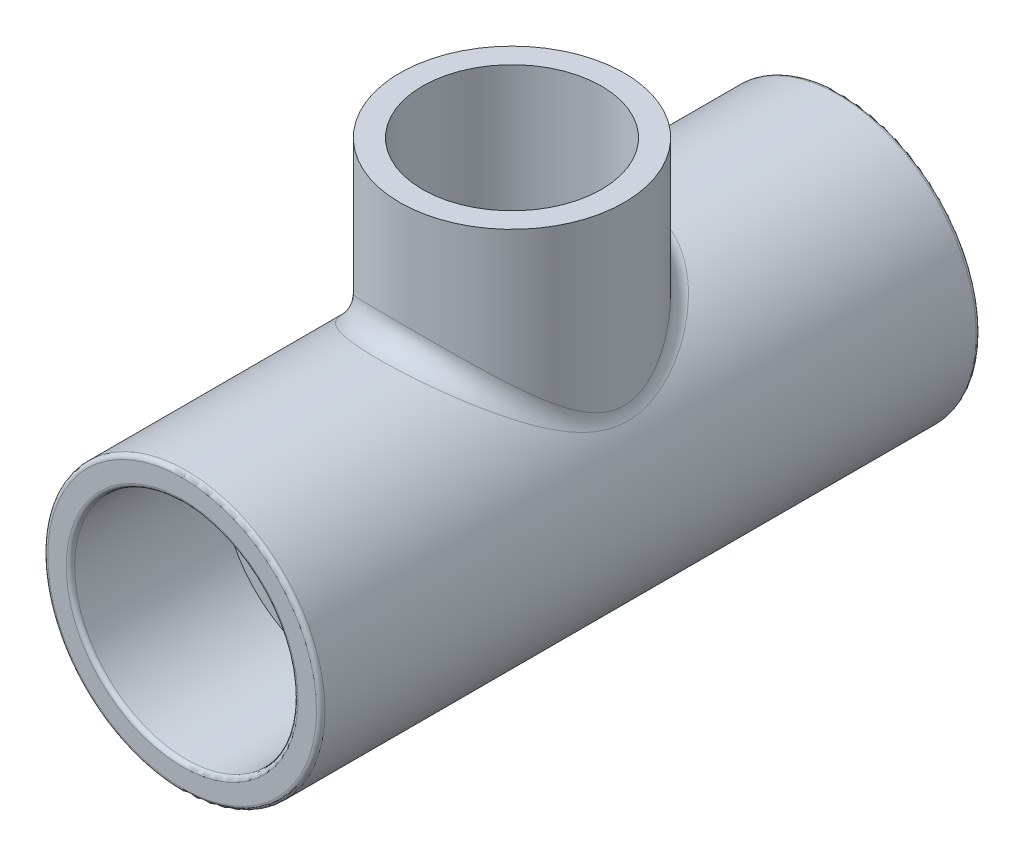
SolidWorks part; units mm, degrees
ref_plane "Front Plane" through (0, 0, 0) normal (0, 0, 1) x (1, 0, 0)
ref_plane "Top Plane" through (0, 0, 0) normal (0, 1, 0) x (1, 0, 0)
ref_plane "Right Plane" through (0, 0, 0) normal (1, 0, 0) x (0, 0, -1)
sketch "Sketch1" plane through (0, 0, 0) normal (0, 0, 1) x (1, 0, 0)
  circle A0 centre (0, 0) radius 656.5
  dimension "D1" = 1313
extrude "Boss-Extrude1" add sketch "Sketch1" along normal blind 1562.5 and the other way blind 1562.5
sketch "Sketch2" plane through (0, 0, 0) normal (0, 1, 0) x (1, 0, 0)
  circle A0 centre (0, 0) radius 531.5
  dimension "D1" = 1063
extrude "Boss-Extrude2" add sketch "Sketch2" along normal blind 1250
sketch "Sketch3" plane through (0, 1250, 0) normal (0, 1, 0) x (1, 0, 0)
  circle A0 centre (0, 0) radius 311
  dimension "D1" = 622
extrude "Cut-Extrude2" cut sketch "Sketch3" against normal blind 1250
sketch "Sketch4" plane through (0, 1250, 0) normal (0, 1, 0) x (1, 0, 0)
  circle A0 centre (0, 0) radius 424
  dimension "D1" = 848
extrude "Cut-Extrude3" cut sketch "Sketch4" against normal blind 690
sketch "Sketch5" plane through (0, 0, 1562.5) normal (0, 0, 1) x (1, 0, 0)
  circle A0 centre (0, 0) radius 412
  dimension "D1" = 824
extrude "Cut-Extrude4" cut sketch "Sketch5" against normal through all
sketch "Sketch6" plane through (0, 0, 1562.5) normal (0, 0, 1) x (1, 0, 0)
  circle A0 centre (0, 0) radius 529
  dimension "D1" = 1058
extrude "Cut-Extrude5" cut sketch "Sketch6" against normal blind 720
sketch "Sketch7" plane through (0, 0, -1562.5) normal (0, 0, -1) x (-1, 0, 0)
  circle A0 centre (0, 0) radius 529
  dimension "D1" = 1058
extrude "Cut-Extrude6" cut sketch "Sketch7" against normal blind 720
fillet "Fillet1" radius 20 2 edges at (656.5, 0, -1562.5) (-529, 0, -1562.5)
fillet "Fillet2" radius 20 2 edges at (656.5, 0, 1562.5) (529, 0, 1562.5)
fillet "Fillet3" radius 100 1 edges at (-51.7907, 654.454, 528.9707)
